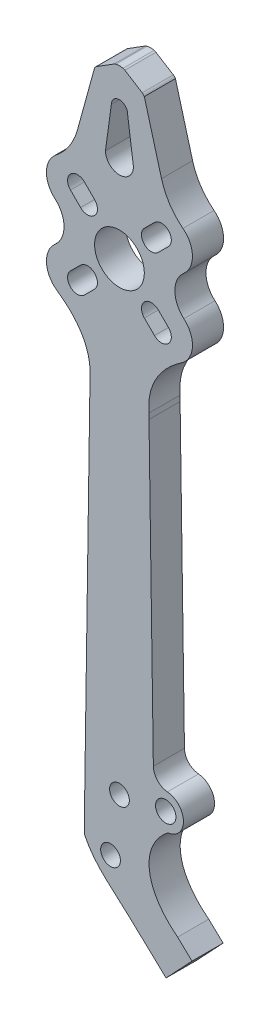
SolidWorks part; units mm, degrees
ref_plane "Alzado" through (0, 0, 0) normal (0, 0, 1) x (1, 0, 0)
ref_plane "Planta" through (0, 0, 0) normal (0, 1, 0) x (1, 0, 0)
ref_plane "Vista lateral" through (0, 0, 0) normal (1, 0, 0) x (0, 0, -1)
sketch "Croquis1" plane through (0, 0, 0) normal (0, 0, 1) x (1, 0, 0)
  line L0 (-2.2478, 13.916) -> (-1.3, 20.8515)
  line L5 (1.4432, 0) -> (-1.4432, 0) construction
  line L6 (0, 26.8758) -> (0, 27) construction
  line L23 (0, 4) -> (2.2899, 4) construction
  line L25 (2.7136, 13.8515) -> (2.2478, 13.916)
  line L26 (0, 0) -> (0, -4) construction
  line L29 (-5.6262, -80) -> (5.6262, -80) construction
  line L31 (-5.6262, -80) -> (-5.6262, -82.9587)
  line L37 (6.4527, -95.4252) -> (1.6612, -90.9174)
  line L38 (11.5591, -91.8588) -> (9.346, -89.7768)
  line L39 (-5.6215, 5.6215) -> (-5.1265, 5.1265) construction
  line L42 (-6.7529, 6.7529) -> (-5.1265, 5.1265) construction
  line L47 (-1, 1) -> (1, -1) construction
  line L48 (-1, -1) -> (1, 1) construction
  line L51 (0, -71.6406) -> (0, -80) construction
  line L54 (-5.6303, 7.8754) -> (-4.004, 6.2491)
  line L57 (6.4527, -95.4252) -> (7.3817, -96.2992)
  line L58 (2.2478, 13.916) -> (1.3, 20.8515)
  line L59 (0, 26.8758) -> (0, 22.1515)
  line L60 (-3.6556, 24.9413) -> (-0.8682, 26.6832)
  line L61 (3.6556, 24.9413) -> (0.8682, 26.6832)
  line L62 (-6.7596, 14.5341) -> (-4, 24.5786)
  line L63 (-10.2131, 9.3289) -> (-10.2129, 9.329)
  line L64 (-4.75, -19.1024) -> (-4.75, -20)
  line L65 (-5.6262, -80) -> (-4.75, -20)
  line L67 (4.75, -19.1024) -> (4.75, -20)
  line L68 (6.7596, 14.5341) -> (4, 24.5786)
  line L69 (-8.5, 0) -> (-4, 0) construction
  line L70 (5.6215, 5.6215) -> (5.1265, 5.1265) construction
  line L71 (7.4909, -96.402) -> (11.692, -91.9365)
  line L72 (7.3817, -96.2992) -> (7.4909, -96.402)
  line L73 (-7.8754, 5.6303) -> (-6.2491, 4.004)
  line L74 (6.7529, 6.7529) -> (5.1265, 5.1265) construction
  line L75 (5.6303, 7.8754) -> (4.004, 6.2491)
  line L76 (7.8754, 5.6303) -> (6.2491, 4.004)
  line L77 (-6.7529, -6.7529) -> (-5.1265, -5.1265) construction
  line L78 (-5.6303, -7.8754) -> (-4.004, -6.2491)
  line L79 (-7.8754, -5.6303) -> (-6.2491, -4.004)
  line L80 (6.7529, -6.7529) -> (5.1265, -5.1265) construction
  line L81 (5.6303, -7.8754) -> (4.004, -6.2491)
  line L82 (7.8754, -5.6303) -> (6.2491, -4.004)
  line L83 (5.6215, -5.6215) -> (5.1265, -5.1265) construction
  line L84 (-5.6215, -5.6215) -> (-5.1265, -5.1265) construction
  line L85 (5.4499, -67.9264) -> (4.75, -20)
  line L87 (11.5591, -91.8588) -> (11.6684, -91.9616)
  circle A5 centre (0, 0) radius 4
  arc A14 (-5.6303, 7.8754) -> (-7.8754, 5.6303) centre (-6.7529, 6.7529) ccw
  arc A15 (-6.2491, 4.004) -> (-4.004, 6.2491) centre (-5.1265, 5.1265) ccw
  arc A22 (0.5754, 26.8066) -> (-0.5754, 26.8066) centre (0, 24.4495) ccw
  arc A45 (1.3, 20.8515) -> (-1.3, 20.8515) centre (0, 20.8515) ccw
  arc A46 (-2.2478, 13.916) -> (2.2478, 13.916) centre (0, 13.916) ccw
  arc A47 (-0.5754, 26.8066) -> (-0.8682, 26.6832) centre (-0.3383, 25.8351) ccw
  arc A48 (-3.6556, 24.9413) -> (-4, 24.5786) centre (-3.1256, 24.0933) ccw
  arc A51 (0.5754, 26.8066) -> (0.8682, 26.6832) centre (0.3383, 25.8351) cw
  arc A52 (3.6556, 24.9413) -> (4, 24.5786) centre (3.1256, 24.0933) cw
  arc A53 (-6.7596, 14.5341) -> (-10.2129, 9.329) centre (-16.4023, 17.1834) cw
  arc A64 (0.1516, 3.9971) -> (0.1507, 4) centre (5.6569, 5.6569) cw
  arc A65 (-10.3568, -3.1643) -> (-10.3568, 3.1643) centre (-13.099, 0) ccw
  arc A70 (-10.2129, 9.329) -> (-10.3568, 3.1643) centre (-7.7372, 6.1872) ccw
  arc A71 (10.2129, 9.329) -> (10.3568, 3.1643) centre (7.7372, 6.1872) cw
  arc A72 (10.3568, -3.1643) -> (10.3568, 3.1643) centre (13.099, 0) cw
  arc A73 (9.9986, -9.4866) -> (10.3568, -3.1643) centre (7.7372, -6.1872) ccw
  arc A75 (6.7596, 14.5341) -> (10.2129, 9.329) centre (16.4023, 17.1834) ccw
  arc A76 (-9.9986, -9.4866) -> (-10.3568, -3.1643) centre (-7.7372, -6.1872) cw
  circle A78 centre (-1.4339, -83.7443) radius 1.59
  arc A81 (5.6303, 7.8754) -> (7.8754, 5.6303) centre (6.7529, 6.7529) cw
  arc A82 (6.2491, 4.004) -> (4.004, 6.2491) centre (5.1265, 5.1265) cw
  arc A83 (-5.6303, -7.8754) -> (-7.8754, -5.6303) centre (-6.7529, -6.7529) cw
  arc A84 (-6.2491, -4.004) -> (-4.004, -6.2491) centre (-5.1265, -5.1265) cw
  arc A85 (5.6303, -7.8754) -> (7.8754, -5.6303) centre (6.7529, -6.7529) ccw
  arc A86 (6.2491, -4.004) -> (4.004, -6.2491) centre (5.1265, -5.1265) ccw
  circle A87 centre (0, -74.6267) radius 1.5875
  arc A88 (7.7949, -76.0437) -> (7.7122, -70.3786) centre (7.4415, -73.2157) ccw
  circle A89 centre (7.4415, -73.2157) radius 1.6367
  arc A91 (7.7122, -70.3786) -> (5.4499, -67.9264) centre (7.9496, -67.8899) cw
  spline S0 degree 3 poles (-4.75, -19.1024) (-4.3548, -14.7385) (-6.9802, -11.5418) (-9.9986, -9.4866) knots 0 0 0 0 1 1 1 1
  spline S1 degree 3 poles (-5.6262, -82.9587) (-3.958, -86.469) (-0.9039, -88.4272) (1.8272, -91.0776) (1.9133, -91.1546) knots 0 0 0 0 0.775056 0.79931 0.79931 0.79931 0.79931
  spline S2 degree 3 poles (4.75, -19.1024) (4.3548, -14.7385) (6.9802, -11.5418) (9.9986, -9.4866) knots 0 0 0 0 1 1 1 1
  spline S3 degree 3 poles (9.346, -89.7768) (3.5789, -85.2688) (3.4676, -79.387) (7.7949, -76.0437) knots 0 0 0 0 1 1 1 1
  point P1 (-5.9397, 5.9397)
  point P24 (5.6569, 5.6569)
  point P27 (6.1872, 6.1872)
  point P39 (5.9397, 5.9397)
  point P46 (-5.9397, -5.9397)
  point P58 (3.0973, 26.3745)
  point P64 (-3.0973, 26.3745)
  point P77 (4.2446, 10.2207)
  point P81 (-4.2446, 10.2207)
  point P92 (-6.1872, 6.1872)
  point P95 (-5.6569, 5.6569)
  point P96 (5.9397, -5.9397)
  point P107 (6.1872, -6.1872)
  point P110 (-5.6569, -5.6569)
  point P111 (-6.1872, -6.1872)
  point P120 (5.4967, -71.1324)
  point P123 (5.6569, -5.6569)
  dimension "D4" = 23
  dimension "D3" = 8
  dimension "D7" = 4.75
  dimension "D8" = 8
  dimension "D9" = 7
  dimension "D13" = 0.15
  dimension "D14" = 2.85
  dimension "D12" = 80
  dimension "D17" = 2.9587
  dimension "D18" = 2.8864
  dimension "D19" = 45
  dimension "D22" = 2.6
  dimension "D23" = 1
  dimension "D6" = 4.5
  dimension "D20" = 10
  dimension "D5" = 1.5875
  dimension "D21" = 3.175
  dimension "D10" = 7
  dimension "D11" = 5.6262
  dimension "D15" = 2
  dimension "D16" = 2
extrude "Saliente-Extruir1" add sketch "Croquis1" along normal blind 5 contours L67 | A22 A5 region at (0.3762, -31.6364, 0)
